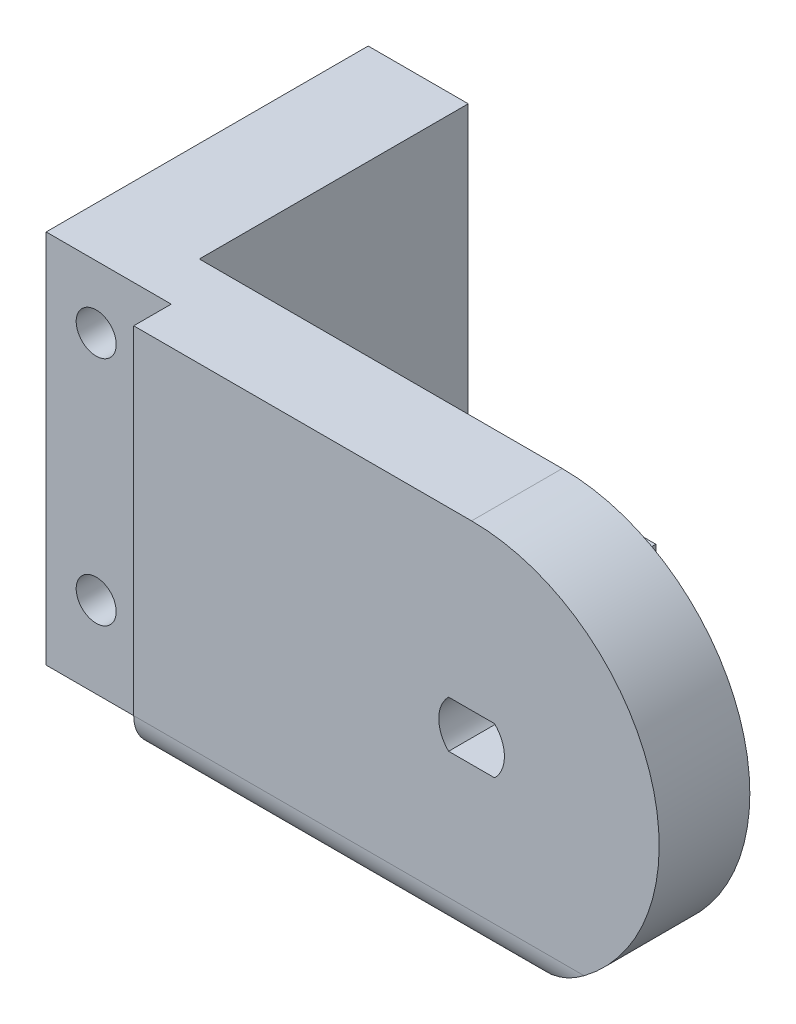
SolidWorks part; units mm, degrees
ref_plane "Front Plane" through (0, 0, 0) normal (0, 0, 1) x (1, 0, 0)
ref_plane "Top Plane" through (0, 0, 0) normal (0, 1, 0) x (1, 0, 0)
ref_plane "Right Plane" through (0, 0, 0) normal (1, 0, 0) x (0, 0, -1)
sketch "Sketch2" plane through (0, 0, -8) normal (0, 0, 1) x (1, 0, 0)
  line L0 (-25.7692, 245.1803) -> (-54.7874, 245.1803)
  line L1 (-54.7874, 245.1803) -> (-54.7874, 215.1803)
  line L2 (-54.7874, 215.1803) -> (-25.7692, 215.1803)
  arc A2 (-25.7692, 215.1803) -> (-25.7692, 245.1803) centre (-25.7692, 230.1803) ccw
  dimension "D1" = 29.0182
extrude "Boss-Extrude1" add sketch "Sketch2" along normal blind 8
sketch "Sketch3" plane through (0, 0, -28) normal (0, 0, -1) x (-1, 0, 0)
  line L3 (25.7692, 215.1803) -> (54.7874, 215.1803)
  line L4 (54.7874, 215.1803) -> (54.7874, 245.1803)
  line L5 (54.7874, 245.1803) -> (25.7692, 245.1803)
  line L6 (25.7692, 215.1803) -> (54.7874, 215.1803)
  line L7 (54.7874, 215.1803) -> (54.7874, 245.1803)
  line L8 (54.7874, 245.1803) -> (25.7692, 245.1803)
  arc A1 (25.7692, 245.1803) -> (25.7692, 215.1803) centre (25.7692, 230.1803) ccw
  arc A2 (25.7692, 245.1803) -> (25.7692, 215.1803) centre (25.7692, 230.1803) ccw
  dimension "D1" = 0
extrude "Boss-Extrude2" add sketch "Sketch3" along normal blind 8 separate body
sketch "Sketch4" plane through (-54.7874, 0, 0) normal (-1, 0, 0) x (0, 0, 1)
  line L1 (-36, 245.1803) -> (0, 245.1803)
  line L2 (-36, 245.1803) -> (-36, 215.1803)
  line L3 (-36, 215.1803) -> (0, 215.1803)
  line L4 (0, 245.1803) -> (0, 215.1803)
extrude "Boss-Extrude3" add sketch "Sketch4" along normal blind 8
sketch "Sketch6" plane through (0, 0, -36) normal (0, 0, -1) x (-1, 0, 0)
  line L0 (23.9321, 232.0553) -> (27.6063, 232.0553)
  line L1 (23.9321, 228.3053) -> (27.6063, 228.3053)
  arc A0 (23.9321, 232.0553) -> (23.9321, 228.3053) centre (25.7692, 230.1803) ccw
  arc A1 (27.6063, 228.3053) -> (27.6063, 232.0553) centre (25.7692, 230.1803) ccw
  dimension "D1" = 1.875
  dimension "D2" = 3.75
extrude "Cut-Extrude1" cut sketch "Sketch6" against normal up to surface (36 mm away) up to face at (-40.5283, 230.1803, 0)
sketch "Sketch7" plane through (-62.7874, 0, 0) normal (-1, 0, 0) x (0, 0, 1)
  line L0 (0, 215.1803) -> (0, 218.1803)
  line L1 (0, 215.1803) -> (0, 245.1803) construction
  line L2 (0, 215.1803) -> (-3, 215.1803)
  line L3 (-36, 215.1803) -> (0, 215.1803) construction
  line L4 (-18, 215.1803) -> (-18, 245.1803) construction
  line L5 (0, 245.1803) -> (-36, 245.1803) construction
  line L6 (-36, 215.1803) -> (-33, 215.1803)
  line L7 (-36, 215.1803) -> (-36, 218.1803)
  arc A0 (0, 218.1803) -> (-3, 215.1803) centre (-3, 218.1803) cw
  arc A1 (-36, 218.1803) -> (-33, 215.1803) centre (-33, 218.1803) ccw
extrude "Cut-Extrude2" cut sketch "Sketch7" against normal through all
sketch "Sketch8" plane through (0, 215.1803, 0) normal (0, -1, 0) x (1, 0, 0)
  line L0 (-54.7874, -8) -> (-25.7692, -8) construction
  line L1 (-56.7874, -28) -> (-39.7874, -28)
  line L2 (-56.7874, -28) -> (-56.7874, -8)
  line L3 (-56.7874, -8) -> (-39.7874, -8)
  line L4 (-39.7874, -28) -> (-39.7874, -8)
extrude "Boss-Extrude5" add sketch "Sketch8" against normal blind 7
sketch "Sketch10" plane through (0, 0, -28) normal (0, 0, 1) x (1, 0, 0)
  line L5 (-54.7874, 222.1803) -> (-39.7874, 222.1803)
  line L6 (-39.7874, 222.1803) -> (-39.7874, 215.1803)
  line L7 (-39.7874, 215.1803) -> (-25.7692, 215.1803)
  line L8 (-25.7692, 245.1803) -> (-54.7874, 245.1803)
  line L9 (-54.7874, 245.1803) -> (-54.7874, 222.1803)
  line L10 (-54.7874, 222.1803) -> (-39.7874, 222.1803)
  line L11 (-39.7874, 222.1803) -> (-39.7874, 215.1803)
  line L12 (-39.7874, 215.1803) -> (-25.7692, 215.1803)
  line L13 (-25.7692, 245.1803) -> (-54.7874, 245.1803)
  line L14 (-54.7874, 245.1803) -> (-54.7874, 222.1803)
  arc A1 (-25.7692, 215.1803) -> (-25.7692, 245.1803) centre (-25.7692, 230.1803) ccw
  arc A2 (-25.7692, 215.1803) -> (-25.7692, 245.1803) centre (-25.7692, 230.1803) ccw
  dimension "D1" = 0
extrude "Cut-Extrude3" cut sketch "Sketch10" against normal blind 0.75
sketch "Sketch11" plane through (0, 0, -8) normal (0, 0, -1) x (-1, 0, 0)
  line L5 (25.7692, 215.1803) -> (39.7874, 215.1803)
  line L6 (39.7874, 215.1803) -> (39.7874, 222.1803)
  line L7 (39.7874, 222.1803) -> (54.7874, 222.1803)
  line L8 (54.7874, 222.1803) -> (54.7874, 245.1803)
  line L9 (54.7874, 245.1803) -> (25.7692, 245.1803)
  line L10 (25.7692, 215.1803) -> (39.7874, 215.1803)
  line L11 (39.7874, 215.1803) -> (39.7874, 222.1803)
  line L12 (39.7874, 222.1803) -> (54.7874, 222.1803)
  line L13 (54.7874, 222.1803) -> (54.7874, 245.1803)
  line L14 (54.7874, 245.1803) -> (25.7692, 245.1803)
  arc A1 (25.7692, 245.1803) -> (25.7692, 215.1803) centre (25.7692, 230.1803) ccw
  arc A2 (25.7692, 245.1803) -> (25.7692, 215.1803) centre (25.7692, 230.1803) ccw
  dimension "D1" = 0
extrude "Cut-Extrude4" cut sketch "Sketch11" against normal blind 0.75
sketch "Sketch13" plane through (0, 0, -36) normal (0, 0, -1) x (-1, 0, 0)
  line L1 (52.7874, 245.1803) -> (65.2203, 245.1803)
  line L2 (52.7874, 245.1803) -> (52.7874, 215.1803)
  line L3 (52.7874, 215.1803) -> (65.2203, 215.1803)
  line L4 (65.2203, 245.1803) -> (65.2203, 215.1803)
extrude "Cut-Extrude6" cut sketch "Sketch13" against normal blind 3
sketch "Sketch14" plane through (0, 0, 0) normal (0, 0, 1) x (1, 0, 0)
  line L4 (-52.7874, 245.1803) -> (-62.7874, 245.1803)
  line L5 (-52.7874, 215.1803) -> (-52.7874, 245.1803)
  line L6 (-62.7874, 215.1803) -> (-52.7874, 215.1803)
  line L7 (-62.7874, 245.1803) -> (-62.7874, 215.1803)
  line L8 (-52.7874, 245.1803) -> (-62.7874, 245.1803)
  line L9 (-52.7874, 215.1803) -> (-52.7874, 245.1803)
  line L10 (-62.7874, 215.1803) -> (-52.7874, 215.1803)
  line L11 (-62.7874, 245.1803) -> (-62.7874, 215.1803)
  dimension "D1" = 0
extrude "Cut-Extrude7" cut sketch "Sketch14" against normal blind 3
sketch "Sketch15" plane through (0, 0, 0) normal (0, 0, 1) x (1, 0, 0)
  spline S0 degree 3 poles (-58.7873, 241.7803) (-61.9873, 241.7803) (-61.9873, 238.5803) (-58.7873, 238.5803) (-55.5873, 238.5803) (-55.5873, 241.7803) (-58.7873, 241.7803) (-61.9873, 241.7803) (-61.9873, 238.5803) knots -0.5 0 0 0 0.5 0.5 0.5 1 1 1 1.5 1.5 1.5 weights 1 0.333333 0.333333 1 0.333333 0.333333 1 0.333333 0.333333 only from (-58.7873, 241.7803) to (-58.7873, 241.7803) construction
  spline S1 degree 3 poles (-58.7873, 223.28) (-61.9873, 223.28) (-61.9873, 220.08) (-58.7873, 220.08) (-55.5873, 220.08) (-55.5873, 223.28) (-58.7873, 223.28) (-61.9873, 223.28) (-61.9873, 220.08) knots -0.5 0 0 0 0.5 0.5 0.5 1 1 1 1.5 1.5 1.5 weights 1 0.333333 0.333333 1 0.333333 0.333333 1 0.333333 0.333333 only from (-58.7873, 223.28) to (-58.7873, 223.28) construction
  spline S2 degree 3 poles (-58.7873, 241.7803) (-61.9873, 241.7803) (-61.9873, 238.5803) (-58.7873, 238.5803) (-55.5873, 238.5803) (-55.5873, 241.7803) (-58.7873, 241.7803) (-61.9873, 241.7803) (-61.9873, 238.5803) knots -0.5 0 0 0 0.5 0.5 0.5 1 1 1 1.5 1.5 1.5 weights 1 0.333333 0.333333 1 0.333333 0.333333 1 0.333333 0.333333 only from (-58.7873, 241.7803) to (-58.7873, 241.7803)
  spline S3 degree 3 poles (-58.7873, 223.28) (-61.9873, 223.28) (-61.9873, 220.08) (-58.7873, 220.08) (-55.5873, 220.08) (-55.5873, 223.28) (-58.7873, 223.28) (-61.9873, 223.28) (-61.9873, 220.08) knots -0.5 0 0 0 0.5 0.5 0.5 1 1 1 1.5 1.5 1.5 weights 1 0.333333 0.333333 1 0.333333 0.333333 1 0.333333 0.333333 only from (-58.7873, 223.28) to (-58.7873, 223.28)
extrude "Cut-Extrude8" cut sketch "Sketch15" against normal up to surface (36 mm away) up to face at (-25.7692, 230.1803, -36)
sketch "Sketch16" plane through (0, 0, -36) normal (0, 0, -1) x (-1, 0, 0)
  line L1 (75.759, 213.0722) -> (7.7191, 213.0722)
  line L2 (75.759, 213.0722) -> (75.759, 247.053)
  line L3 (75.759, 247.053) -> (7.7191, 247.053)
  line L4 (7.7191, 213.0722) -> (7.7191, 247.053)
extrude "Cut-Extrude9" cut sketch "Sketch16" against normal up to surface (7.25 mm away) up to face at (-37.6147, 227.5136, -28.75)
